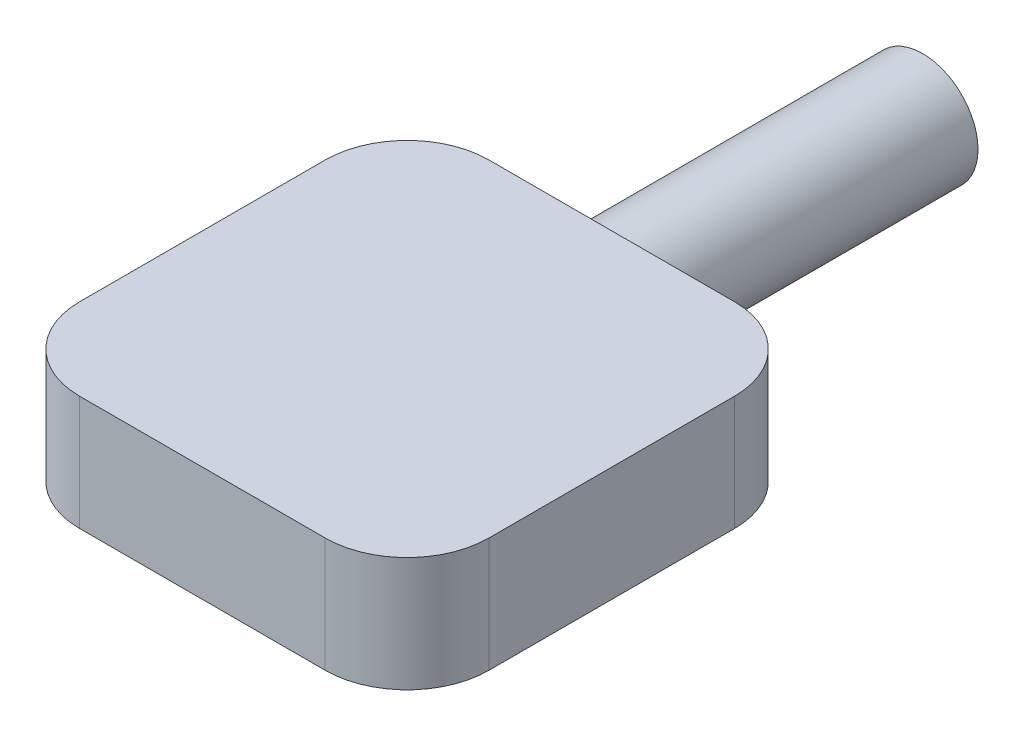
SolidWorks part; units mm, degrees
material "6061 Alloy"
ref_plane "Front Plane" through (0, 0, 0) normal (0, 0, 1) x (1, 0, 0)
ref_plane "Top Plane" through (0, 0, 0) normal (0, 1, 0) x (1, 0, 0)
ref_plane "Right Plane" through (0, 0, 0) normal (1, 0, 0) x (0, 0, -1)
sketch "Sketch1" plane through (0, 0, 0) normal (0, 0, 1) x (1, 0, 0)
  circle A0 centre (0, 0) radius 6.75
  dimension "D1" = 13.5
extrude "Boss-Extrude1" add sketch "Sketch1" along normal blind 73 and the other way blind 10
sketch "Sketch2" plane through (0, 0, 0) normal (0, 1, 0) x (1, 0, 0)
  line L1 (-15, -78) -> (15, -78)
  line L2 (-25, -68) -> (-25, -38)
  line L3 (-15, -28) -> (15, -28)
  line L4 (25, -68) -> (25, -38)
  arc A0 (15, -28) -> (25, -38) centre (15, -38) cw
  arc A1 (25, -68) -> (15, -78) centre (15, -68) cw
  arc A2 (-25, -38) -> (-15, -28) centre (-15, -38) cw
  arc A3 (-25, -68) -> (-15, -78) centre (-15, -68) ccw
  point P4 (25, -53)
  point P6 (0, -78)
  point P11 (25, -78)
  point P16 (-25, -78)
  dimension "D3" = 10
  dimension "D1" = 53
  dimension "D2" = 50
  dimension "D4" = 50
extrude "Boss-Extrude2" add sketch "Sketch2" along normal blind 7 and the other way blind 7
